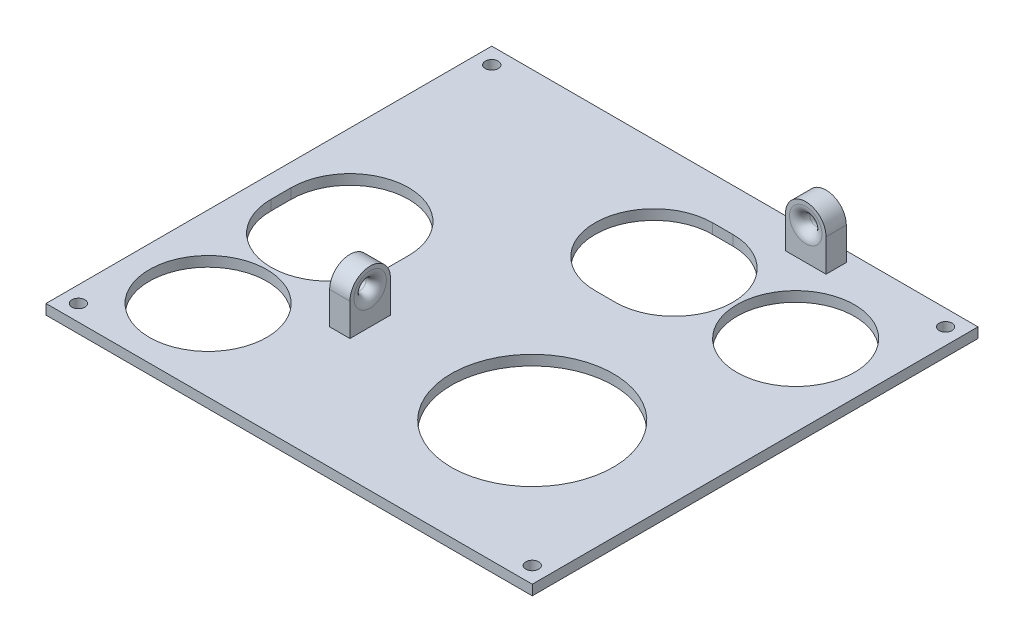
SolidWorks part; units mm, degrees
ref_plane "前视基准面" through (0, 0, 0) normal (0, 0, 1) x (1, 0, 0)
ref_plane "上视基准面" through (0, 0, 0) normal (0, 1, 0) x (1, 0, 0)
ref_plane "右视基准面" through (0, 0, 0) normal (1, 0, 0) x (0, 0, -1)
sketch "Sketch1" plane through (0, 0, 0) normal (0, 1, 0) x (1, 0, 0)
  line L1 (-60, 55) -> (60, 55)
  line L2 (-60, 55) -> (-60, -55)
  line L3 (-60, -55) -> (60, -55)
  line L4 (60, 55) -> (60, -55)
  line L5 (0, -55) -> (0, 55) construction
  line L6 (-60, 0) -> (60, 0) construction
  point P0 (0, 0)
  dimension "D1" = 120
  dimension "D2" = 110
extrude "Boss-Extrude1" add sketch "Sketch1" along normal blind 2.5
sketch "Sketch2" plane through (0, 2.5, 0) normal (0, 1, 0) x (1, 0, 0)
  line L0 (60, -55) -> (60, 55) construction
  line L1 (60, 55) -> (-60, 55) construction
  line L2 (-60, -55) -> (60, -55) construction
  line L3 (-60, 55) -> (-60, -55) construction
  line L4 (10, 30) -> (19.5, 30) construction
  line L5 (-40, -5) -> (-40, -14.5) construction
  line L6 (40, 30) -> (49.5, 30) construction
  line L8 (-40, -35) -> (-40, -44.5) construction
  circle A0 centre (40, 30) radius 14.5
  circle A1 centre (10, 30) radius 14.5
  circle A2 centre (-40, -5) radius 14.5
  circle A3 centre (-40, -35) radius 14.5
  circle A5 centre (19.5, 30) radius 1.6 construction
  circle A6 centre (49.5, 30) radius 1.6 construction
  circle A7 centre (-40, -14.5) radius 1.6 construction
  circle A8 centre (-40, -44.5) radius 1.6 construction
  circle A9 centre (10, 20.5) radius 1.6 construction
  circle A10 centre (0.5, 30) radius 1.6 construction
  circle A11 centre (10, 39.5) radius 1.6 construction
  circle A12 centre (40, 20.5) radius 1.6 construction
  circle A13 centre (30.5, 30) radius 1.6 construction
  circle A14 centre (40, 39.5) radius 1.6 construction
  circle A15 centre (-49.5, -35) radius 1.6 construction
  circle A16 centre (-40, -25.5) radius 1.6 construction
  circle A17 centre (-30.5, -35) radius 1.6 construction
  circle A19 centre (-49.5, -5) radius 1.6 construction
  circle A21 centre (-40, 4.5) radius 1.6 construction
  circle A23 centre (-30.5, -5) radius 1.6 construction
  circle A24 centre (-0.5, -5) radius 1.6 [skipped]
  circle A25 centre (-79.5, -5) radius 1.6 [skipped]
  circle A26 centre (-40, 34.5) radius 1.6 [skipped]
  point P33 (10, 30)
  point P40 (40, 30)
  point P47 (-40, -35)
  point P60 (-40, -5)
  dimension "D1" = 29
  dimension "D8" = 3.2
  dimension "D11" = 3.2
  dimension "D2" = 20
  dimension "D3" = 25
  dimension "D4" = 20
  dimension "D5" = 20
  dimension "D6" = 30
  dimension "D7" = 30
  dimension "D9" = 9.5
  dimension "D10" = 9.5
  dimension "D12" = 9.5
  dimension "D13" = 4
  dimension "D14" = 4
  dimension "D15" = 4
  dimension "D16" = 4
extrude "Cut-Extrude1" cut sketch "Sketch2" against normal blind 4
sketch "Sketch3" plane through (0, 2.5, 0) normal (0, 1, 0) x (1, 0, 0)
  line L0 (-40, -5) -> (-40, -35) construction
  line L2 (10, 30) -> (40, 30) construction
  line L4 (-40, -20) -> (25, -20) construction
  line L5 (25, -20) -> (25, 30) construction
  circle A0 centre (25, -20) radius 20
  circle A1 centre (25, -8.75) radius 1.6 construction
  circle A2 centre (36.25, -20) radius 1.6 construction
  circle A3 centre (25, -31.25) radius 1.6 construction
  circle A4 centre (13.75, -20) radius 1.6 construction
  point P23 (25, -20)
  dimension "D1" = 40
  dimension "D2" = 11.25
  dimension "D3" = 3.2
  dimension "D4" = 4
extrude "Cut-Extrude2" cut sketch "Sketch3" against normal blind 10
sketch "Sketch5" plane through (0, 2.5, 0) normal (0, 1, 0) x (1, 0, 0)
  line L0 (-60, -55) -> (60, -55) construction
  line L1 (-56, -51) -> (56, -51) construction
  line L2 (-56, -51) -> (-56, 51) construction
  line L3 (-56, 51) -> (56, 51) construction
  line L4 (56, -51) -> (56, 51) construction
  line L5 (0, 51) -> (0, -51) construction
  line L6 (-56, 0) -> (56, 0) construction
  line L7 (-60, 55) -> (-60, -55) construction
  circle A0 centre (-56, 51) radius 1.6
  circle A1 centre (56, 51) radius 1.6
  circle A2 centre (56, -51) radius 1.6
  circle A3 centre (-56, -51) radius 1.6
  point P0 (0, 0)
  dimension "D1" = 3.2
  dimension "D2" = 4
  dimension "D3" = 4
extrude "Cut-Extrude5" cut sketch "Sketch5" against normal blind 10
sketch "Sketch7" plane through (0, 2.5, 0) normal (0, 1, 0) x (1, 0, 0)
  line L0 (-40, -5) -> (-40, 0) construction
  line L1 (-54.5, -5) -> (-54.5, 0)
  line L2 (-25.5, -5) -> (-25.5, 0)
  line L3 (10, 30) -> (5, 30) construction
  line L4 (10, 15.5) -> (5, 15.5)
  line L5 (10, 44.5) -> (5, 44.5)
  arc A0 (-54.5, -5) -> (-25.5, -5) centre (-40, -5) ccw
  arc A1 (-25.5, 0) -> (-54.5, 0) centre (-40, 0) ccw
  arc A2 (10, 15.5) -> (10, 44.5) centre (10, 30) ccw
  arc A3 (5, 44.5) -> (5, 15.5) centre (5, 30) ccw
  circle A4 centre (-40, -5) radius 14.5 construction
  point P3 (-40, -2.5)
  point P10 (7.5, 30)
  dimension "D1" = 5
extrude "Cut-Extrude6" cut sketch "Sketch7" against normal blind 10
sketch "Sketch8" plane through (0, 2.5, 0) normal (0, 1, 0) x (1, 0, 0)
  line L0 (-40, -35) -> (-40, -5) construction
  line L2 (10, 30) -> (40, 30) construction
  line L3 (-20, -15) -> (-15, -15)
  line L4 (-20, -15) -> (-20, -25)
  line L5 (-20, -25) -> (-15, -25)
  line L6 (-15, -15) -> (-15, -25)
  line L7 (-17.5, -25) -> (-17.5, -15) construction
  line L8 (-20, -20) -> (-15, -20) construction
  line L9 (20, 52.5) -> (30, 52.5)
  line L10 (20, 52.5) -> (20, 47.5)
  line L11 (20, 47.5) -> (30, 47.5)
  line L12 (30, 52.5) -> (30, 47.5)
  line L13 (25, 47.5) -> (25, 52.5) construction
  line L14 (20, 50) -> (30, 50) construction
  point P4 (-17.5, -20)
  point P12 (25, 50)
  point P20 (-40, -20)
  point P22 (25, 30)
  dimension "D1" = 5
  dimension "D2" = 10
  dimension "D3" = 22.5
  dimension "D4" = 20
extrude "Boss-Extrude2" add sketch "Sketch8" along normal blind 14
sketch "Sketch9" plane through (0, 0, -47.5) normal (0, 0, 1) x (1, 0, 0)
  line L0 (-60, 2.5) -> (60, 2.5) construction
  line L1 (25, 16.5) -> (25, 10.5) construction
  line L2 (20, 16.5) -> (30, 16.5) construction
  line L3 (20, 16.5) -> (20, 2.5) construction
  line L4 (30, 16.5) -> (30, 2.5) construction
  line L5 (20, 10.5) -> (20, 22.099)
  line L6 (20, 22.099) -> (30, 22.099)
  line L7 (30, 22.099) -> (30, 10.5)
  circle A0 centre (25, 10.5) radius 1.5
  arc A1 (20, 10.5) -> (30, 10.5) centre (25, 10.5) cw
  dimension "D1" = 8
  dimension "D2" = 3
extrude "Cut-Extrude7" cut sketch "Sketch9" against normal through all
sketch "Sketch10" plane through (-15, 0, 0) normal (1, 0, 0) x (0, 0, -1)
  line L0 (-25, 16.5) -> (-25, 2.5) construction
  line L1 (-15, 16.5) -> (-15, 2.5) construction
  line L2 (-55, 2.5) -> (55, 2.5) construction
  line L3 (-25, 10.5) -> (-25, 23.5311)
  line L4 (-25, 23.5311) -> (-15, 23.5311)
  line L5 (-15, 23.5311) -> (-15, 10.5)
  circle A0 centre (-20, 10.5) radius 1.5
  arc A1 (-25, 10.5) -> (-15, 10.5) centre (-20, 10.5) cw
  point P13 (-20, 23.5311)
  dimension "D1" = 3
  dimension "D2" = 8
extrude "Cut-Extrude8" cut sketch "Sketch10" against normal blind 5
fillet "Fillet1" radius 2.5 4 edges at (26.5, 10.5, -52.5) (26.5, 10.5, -47.5) (-20, 10.5, 18.5) (-15, 10.5, 18.5)
equation "\"D4@Sketch2\"=\"D5@Sketch2\""
equation "\"D2@Sketch2\"=\"D5@Sketch2\""
equation "\"D3@Sketch5\"=\"D2@Sketch5\""
equation "\"D7@Sketch2\"=\"D6@Sketch2\""
